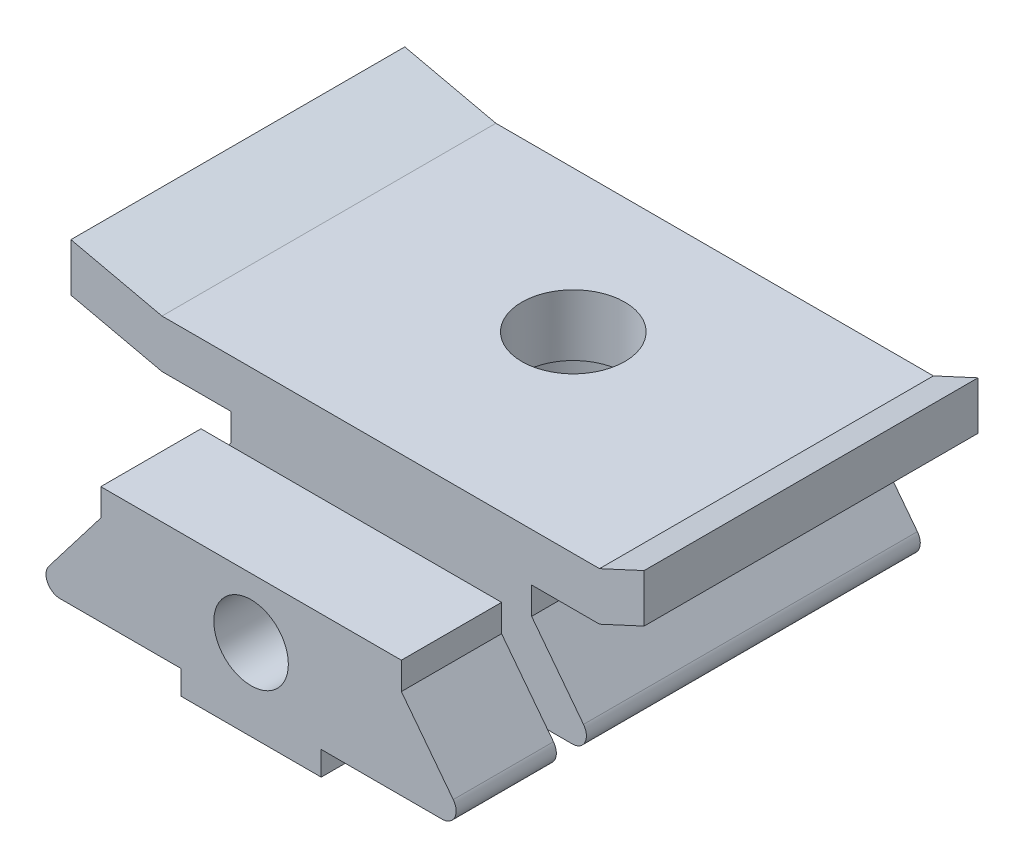
SolidWorks part; units mm, degrees
ref_plane "Front Plane" through (0, 0, 0) normal (0, 0, 1) x (1, 0, 0)
ref_plane "Top Plane" through (0, 0, 0) normal (0, 1, 0) x (1, 0, 0)
ref_plane "Right Plane" through (0, 0, 0) normal (1, 0, 0) x (0, 0, -1)
sketch "Sketch1" plane through (0, 0, 0) normal (0, 0, 1) x (1, 0, 0)
  line L0 (-13.8996, -14.0535) -> (13.828, -14.0535)
  line L1 (13.828, -14.0535) -> (13.828, -17.1015)
  line L2 (13.828, -17.1015) -> (9.525, -17.1015)
  line L3 (9.525, -17.1015) -> (9.525, -18.824)
  line L4 (9.525, -18.824) -> (12.8129, -23.1088)
  line L5 (12.1076, -24.539) -> (-12.1076, -24.539)
  line L6 (-12.8129, -23.1088) -> (-9.525, -18.824)
  line L7 (-9.525, -18.824) -> (-9.525, -17.1015)
  line L8 (-9.525, -17.1015) -> (-13.8996, -17.1015)
  line L9 (-13.8996, -17.1015) -> (-13.8996, -14.0535)
  line L10 (13.828, -14.0535) -> (-13.828, -14.0535) construction
  line L15 (-13.8996, -14.0535) -> (-19.6713, -12.7462)
  line L16 (-19.6713, -12.7462) -> (-19.6713, -15.7942)
  line L17 (-19.6713, -15.7942) -> (-13.8996, -17.1015)
  line L19 (13.828, -14.0535) -> (16.6541, -12.7462)
  line L20 (16.6541, -12.7462) -> (16.6541, -15.7942)
  line L21 (16.6541, -15.7942) -> (13.828, -17.1015)
  line L22 (-13.1264, -23.5174) -> (-9.525, -18.824) construction
  line L23 (9.525, -18.824) -> (13.1264, -23.5174) construction
  line L24 (-9.525, -18.824) -> (-9.525, -17.2285) construction
  arc A0 (12.8129, -23.1088) -> (12.1076, -24.539) centre (12.1076, -23.65) cw
  arc A1 (-12.1076, -24.539) -> (-12.8129, -23.1088) centre (-12.1076, -23.65) cw
  dimension "D1" = 0.889
  dimension "D2" = 5.715
  dimension "D3" = 3.048
extrude "Boss-Extrude1" add sketch "Sketch1" along normal blind 21.1582 contours A1 L5 A0 L4 L3 L2 L1 L0 L9 L8 L7 L6 | L21 L20 L19 L1 | L16 L17 L9 L15 region at (-0.0121, -19.2091, 0) region at (-16.7854, -14.9238, 0) region at (15.2411, -14.9238, 0)
ref_plane "Plane1" through (0, -1.5917, 22.7628) normal (0, -0.0698, 0.9976) x (1, 0, 0)
sketch "Sketch5" plane through (0, -1.5917, 22.7628) normal (0, -0.0698, 0.9976) x (1, 0, 0)
  line L1 (-4.445, -28.0833) -> (4.445, -28.0833)
  line L2 (-4.445, -28.0833) -> (-4.445, -21.7333)
  line L3 (-4.445, -21.7333) -> (4.445, -21.7333)
  line L4 (4.445, -28.0833) -> (4.445, -21.7333)
  line L5 (-4.445, -28.0833) -> (4.445, -21.7333) construction
  line L6 (-4.445, -21.7333) -> (4.445, -28.0833) construction
  line L7 (12.1076, -23.0033) -> (-12.1076, -23.0033) construction
  point P0 (0, -24.9083)
  dimension "D1" = 6.35
  dimension "D2" = 8.89
  dimension "D3" = 1.27
extrude "Cut-Extrude2" cut sketch "Sketch5" against normal blind 40
sketch "Sketch7" plane through (0, 0, 21.1582) normal (0, 0, -1) x (-1, 0, 0)
  line L0 (-9.525, -17.1015) -> (9.525, -17.1015)
  line L1 (-4.445, -24.539) -> (-4.445, -26.063)
  line L2 (-4.445, -26.063) -> (4.445, -26.063)
  line L3 (4.445, -26.063) -> (4.445, -24.539)
  line L4 (4.445, -26.063) -> (-4.445, -26.063) construction
  line L18 (-12.1076, -24.539) -> (-4.445, -24.539)
  line L19 (-4.445, -24.539) -> (-4.445, -21.7864)
  line L20 (-4.445, -21.7864) -> (4.445, -21.7864)
  line L21 (4.445, -21.7864) -> (4.445, -24.539)
  line L22 (4.445, -24.539) -> (12.1076, -24.539)
  line L23 (12.8129, -23.1088) -> (9.525, -18.824)
  line L24 (9.525, -18.824) -> (9.525, -17.1015)
  line L25 (9.525, -17.1015) -> (13.8996, -17.1015)
  line L26 (13.8996, -17.1015) -> (19.6713, -15.7942)
  line L27 (19.6713, -15.7942) -> (19.6713, -12.7462)
  line L28 (19.6713, -12.7462) -> (13.8996, -14.0535)
  line L29 (13.8996, -14.0535) -> (-13.828, -14.0535)
  line L30 (-13.828, -14.0535) -> (-16.6541, -12.7462)
  line L31 (-16.6541, -12.7462) -> (-16.6541, -15.7942)
  line L32 (-16.6541, -15.7942) -> (-13.828, -17.1015)
  line L33 (-13.828, -17.1015) -> (-9.525, -17.1015)
  line L34 (-9.525, -17.1015) -> (-9.525, -18.824)
  line L35 (-9.525, -18.824) -> (-12.8129, -23.1088)
  line L36 (-12.1076, -24.539) -> (-4.445, -24.539)
  line L40 (4.445, -24.539) -> (12.1076, -24.539)
  line L41 (12.8129, -23.1088) -> (9.525, -18.824)
  line L42 (9.525, -18.824) -> (9.525, -17.1015)
  line L52 (-9.525, -17.1015) -> (-9.525, -18.824)
  line L53 (-9.525, -18.824) -> (-12.8129, -23.1088)
  arc A2 (12.1076, -24.539) -> (12.8129, -23.1088) centre (12.1076, -23.65) ccw
  arc A3 (-12.8129, -23.1088) -> (-12.1076, -24.539) centre (-12.1076, -23.65) ccw
  arc A4 (12.1076, -24.539) -> (12.8129, -23.1088) centre (12.1076, -23.65) ccw
  arc A5 (-12.8129, -23.1088) -> (-12.1076, -24.539) centre (-12.1076, -23.65) ccw
  dimension "D1" = 0
extrude "Boss-Extrude2" add sketch "Sketch7" along normal up to surface (21.1582 mm away) and the other way blind 8.255 separate body contours L2 L3 L40 A4 L41 L42 L0 L52 L53 A5 L36 L1 up to face at (-0.3089, -18.9813, 0)
sketch "Sketch8" plane through (0, 0, 0) normal (1, 0, 0) x (0, 0, -1)
  line L0 (-23.0632, -15.8819) -> (-23.0632, -23.2659)
  line L1 (-21.1582, -23.2659) -> (3.175, -21.5644)
  line L2 (3.175, -21.5644) -> (3.175, -15.8819)
  line L3 (3.175, -15.8819) -> (-23.0632, -15.8819)
  line L4 (-29.4132, -17.1015) -> (0, -17.1015) construction
  line L5 (-21.1582, -12.7462) -> (-21.1582, -15.7942) construction
  line L6 (0, -21.7864) -> (-21.1582, -23.2659) construction
  line L7 (0, -18.824) -> (0, -17.1015) construction
  line L8 (-21.1582, -23.2659) -> (-23.0632, -23.2659)
  dimension "D1" = 1.2196
  dimension "D2" = 1.905
  dimension "D3" = 3.175
extrude "Cut-Extrude3" cut sketch "Sketch8" against normal through all both and the other way through all contours L3 L0 L8 L1 L2
sketch "Sketch9" plane through (0, -24.539, 0) normal (0, -1, 0) x (1, 0, 0)
  line L0 (-12.9093, 23.0632) -> (12.9093, 23.0632) construction
  line L1 (-4.445, 23.0632) -> (-14.1312, 23.0632)
  line L2 (-4.445, 23.0632) -> (-4.445, -0.0455)
  line L3 (-4.445, -0.0455) -> (-14.1312, -0.0455)
  line L4 (-14.1312, 23.0632) -> (-14.1312, -0.0455)
  line L5 (4.445, 23.0632) -> (14.1312, 23.0632)
  line L6 (4.445, 23.0632) -> (4.445, -0.0455)
  line L7 (4.445, -0.0455) -> (14.1312, -0.0455)
  line L8 (14.1312, 23.0632) -> (14.1312, -0.0455)
  line L9 (4.445, 29.4132) -> (4.445, 0) construction
  line L10 (-4.445, 29.4132) -> (-4.445, 0) construction
  dimension "D1" = 9.6862
  dimension "D2" = 23.1087
extrude "Cut-Extrude4" cut sketch "Sketch9" against normal blind 14.097
sketch "Sketch10" plane through (0, 0, 29.4132) normal (0, 0, 1) x (1, 0, 0)
  line L0 (-4.445, -23.2659) -> (4.445, -23.2659) construction
  circle A0 centre (0, -20.9037) radius 2.3622
  dimension "D1" = 4.7244
extrude "Cut-Extrude5" cut sketch "Sketch10" against normal blind 14.097
hole_wizard "CBORE for 1/4 Socket Head Cap Screw1" positions "Sketch4" profile "Sketch3" counterbore size "1/4" standard "ANSI Inch"
sketch "Sketch4" plane through (0, -24.539, 0) normal (0, -1, 0) x (-1, 0, 0)
  point P0 (0, -8.992)
sketch "Sketch3" plane through (0, -24.539, 8.992) normal (1, 0, 0) x (0, 0, -1)
  line L0 (0, 0) -> (0, 14.9659)
  line L1 (0, 14.9659) -> (3.2639, 13.0048)
  line L2 (3.2639, 13.0048) -> (3.2639, 6.604)
  line L3 (3.2639, 6.604) -> (4.8895, 6.604)
  line L4 (4.8895, 6.604) -> (4.8895, 0)
  line L5 (4.8895, 0) -> (0, 0)
  line L10 (0, 14.9659) -> (-3.2639, 13.0048) construction
  line L11 (0, -6.35) -> (0, 107.95) construction
  dimension "Hole Dia." = 6.5278
  dimension "Hole Depth" = 13.0048
  dimension "C'Bore Dia." = 9.779
  dimension "C'Bore Depth" = 6.604
  dimension "Drill Angle" = 118
